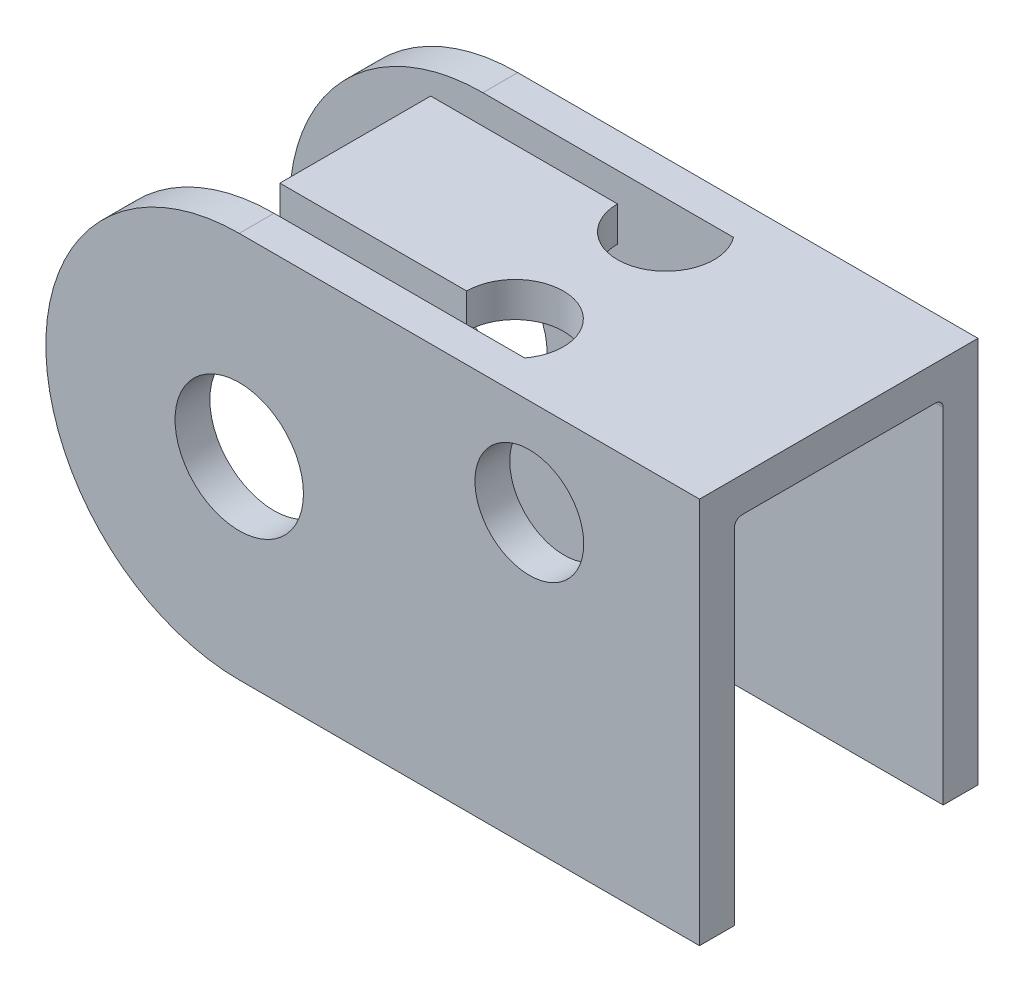
SolidWorks part; units mm, degrees
ref_plane "Front Plane" through (0, 0, 0) normal (0, 0, 1) x (1, 0, 0)
ref_plane "Top Plane" through (0, 0, 0) normal (0, 1, 0) x (1, 0, 0)
ref_plane "Right Plane" through (0, 0, 0) normal (1, 0, 0) x (0, 0, -1)
sketch "Sketch1" plane through (0, 0, 0) normal (0, 1, 0) x (1, 0, 0)
  line L1 (-4.0767, 4.572) -> (4.0767, 4.572)
  line L2 (-4.0767, 4.572) -> (-4.0767, -4.572)
  line L3 (-4.0767, -4.572) -> (4.0767, -4.572)
  line L4 (4.0767, 4.572) -> (4.0767, -4.572)
  line L5 (-4.0767, 4.572) -> (4.0767, -4.572) construction
  line L6 (-4.0767, -4.572) -> (4.0767, 4.572) construction
  point P0 (0, 0)
  dimension "D1" = 8.1534
  dimension "D2" = 9.144
extrude "Boss-Extrude1" add sketch "Sketch1" along normal blind 1.143
sketch "Sketch2" plane through (0, 0, 0) normal (0, 1, 0) x (1, 0, 0)
  line L0 (4.0767, -4.572) -> (4.0767, 4.572) construction
  line L1 (-11.7983, 2.4765) -> (-5.6642, 2.4765)
  line L2 (-11.7983, 2.4765) -> (-11.7983, -2.4765)
  line L3 (-11.7983, -2.4765) -> (-5.6642, -2.4765)
  line L5 (-11.7983, 2.4765) -> (-5.4129, -1.6194) construction
  line L6 (-11.7983, -2.4765) -> (-5.4129, 1.6194) construction
  line L7 (-4.0767, 4.572) -> (-4.0767, -4.572) construction
  line L8 (-4.0767, 4.572) -> (-4.0767, 4.064)
  line L10 (-4.0767, -4.064) -> (-4.0767, -4.572)
  line L11 (-4.0767, 4.572) -> (4.0767, 4.572)
  line L12 (4.0767, 4.572) -> (4.0767, -4.572)
  line L13 (4.0767, -4.572) -> (-4.0767, -4.572)
  arc A0 (-4.0767, -4.064) -> (-5.6642, -2.4765) centre (-4.0767, -2.4765) ccw
  arc A1 (-5.6642, 2.4765) -> (-4.0767, 4.064) centre (-4.0767, 2.4765) ccw
  point P0 (-7.9375, 0)
  dimension "D3" = 3.175
  dimension "D1" = 4.953
  dimension "D2" = 15.875
extrude "Boss-Extrude2" add sketch "Sketch2" along normal blind 1.143
sketch "Sketch3" plane through (0, 1.143, 0) normal (0, 1, 0) x (1, 0, 0)
  circle A0 centre (-4.0767, 2.4765) radius 1.5875
  circle A1 centre (-4.0767, -2.4765) radius 1.5875
extrude "Cut-Extrude1" cut sketch "Sketch3" against normal blind 1.143
sketch "Sketch4" plane through (0, 0, 4.572) normal (0, 0, 1) x (1, 0, 0)
  line L1 (4.0767, 1.143) -> (-17.3863, 1.143)
  line L2 (4.0767, 1.143) -> (4.0767, -11.557)
  line L3 (4.0767, -11.557) -> (-17.3863, -11.557)
  line L4 (-17.3863, 1.143) -> (-17.3863, -11.557)
  dimension "D1" = 21.463
  dimension "D2" = 12.7
extrude "Boss-Extrude3" add sketch "Sketch4" against normal blind 1.143
hole_wizard "9/64 (0.14063) Diameter Hole1" positions "Sketch5" profile "Sketch6" hole size "9/64" standard "ANSI Inch" end condition through all
sketch "Sketch5" plane through (0, 0, 4.572) normal (0, 0, 1) x (1, 0, 0)
  line L0 (-17.3863, 1.143) -> (4.0767, 1.143) construction
  line L1 (-17.3863, 1.143) -> (-17.3863, -11.557) construction
  point P0 (-1.5113, -2.032)
  dimension "D1" = 3.175
  dimension "D2" = 15.875
sketch "Sketch6" plane through (-1.5113, -2.032, 4.572) normal (1, 0, 0) x (0, -1, 0)
  line L0 (0, 0) -> (0, 9.144)
  line L1 (0, 9.144) -> (1.786, 9.144)
  line L2 (1.786, 9.144) -> (1.786, 0)
  line L5 (1.786, 0) -> (0, 0)
  line L11 (0, -6.35) -> (0, 107.95) construction
  dimension "Thru Hole Dia." = 3.572
  dimension "Thru Hole Depth" = 9.144
fillet "Fillet1" 2 edges at (-17.3863, 1.143, 4.0005) (-17.3863, -11.557, 4.0005) type full round first side face at (-6.357, 1.143, 0.248) second side face at (-6.6548, -11.557, 4.0005) middle face at (-17.3863, -5.207, 4.0005)
hole_wizard "#19 (0.166) Diameter Hole1" positions "Sketch7" profile "Sketch8" hole size "#19" standard "ANSI Inch" end condition through all
sketch "Sketch7" plane through (0, 0, 4.572) normal (0, 0, 1) x (1, 0, 0)
  point P0 (-11.0363, -5.207)
sketch "Sketch8" plane through (-11.0363, -5.207, 4.572) normal (1, 0, 0) x (0, -1, 0)
  line L0 (0, 0) -> (0, 9.144)
  line L1 (0, 9.144) -> (2.1082, 9.144)
  line L2 (2.1082, 9.144) -> (2.1082, 0)
  line L5 (2.1082, 0) -> (0, 0)
  line L11 (0, -6.35) -> (0, 107.95) construction
  dimension "Thru Hole Dia." = 4.2164
  dimension "Thru Hole Depth" = 9.144
mirror "Mirror1" about plane through (0, 0, 0) normal (0, 0, 1) of "Boss-Extrude3", "9/64 (0.14063) Diameter Hole1", "Fillet1", "#19 (0.166) Diameter Hole1"
fillet "Fillet2" radius 0.254 2 edges at (0.635, 0, 3.429) (0.635, 0, -3.429)
